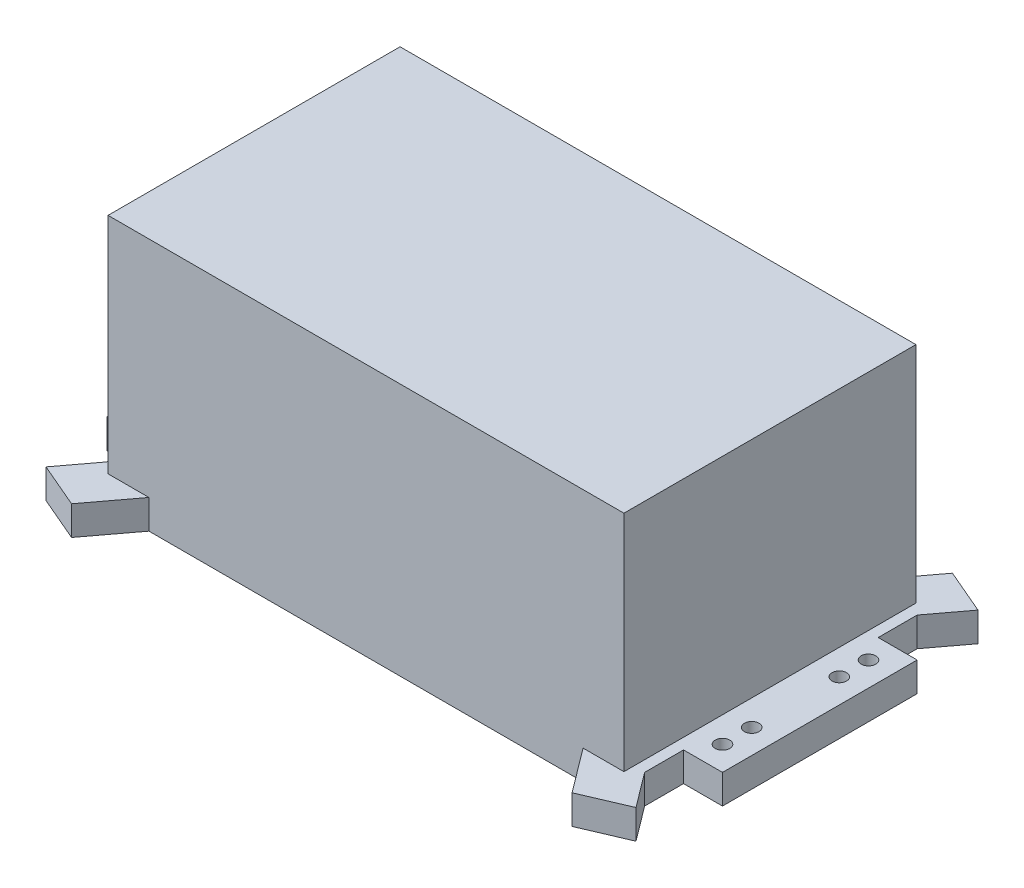
SolidWorks part; units mm, degrees
ref_plane "前视基准面" through (0, 0, 0) normal (0, 0, 1) x (1, 0, 0)
ref_plane "上视基准面" through (0, 0, 0) normal (0, 1, 0) x (1, 0, 0)
ref_plane "右视基准面" through (0, 0, 0) normal (1, 0, 0) x (0, 0, -1)
sketch "草图1" plane through (0, 0, 0) normal (0, 1, 0) x (1, 0, 0)
  line L0 (-65.7171, 0) -> (87.7991, 0) construction
  line L1 (44.6018, -30) -> (-44.6018, -30)
  line L3 (44.6018, 30) -> (-44.6018, 30)
  line L5 (53, -30) -> (-53, 30) construction
  line L6 (53, 30) -> (-53, -30) construction
  line L8 (63.25, -20) -> (63.25, 20)
  line L10 (-63.25, -20) -> (-63.25, 20)
  line L11 (63.25, 20) -> (55.25, 20)
  line L12 (55.25, 20) -> (55.25, 28)
  line L13 (55.25, 28) -> (60.6154, 35.1388)
  line L14 (60.6154, 35.1388) -> (51.4231, 39.0759)
  line L15 (51.4231, 39.0759) -> (44.6018, 30)
  line L16 (63.25, -20) -> (55.25, -20)
  line L17 (55.25, -20) -> (55.25, -28)
  line L18 (55.25, -28) -> (60.6154, -35.1388)
  line L19 (60.6154, -35.1388) -> (51.4231, -39.0759)
  line L20 (51.4231, -39.0759) -> (44.6018, -30)
  line L21 (0, -33.7082) -> (0, 42.5182) construction
  line L22 (-51.4231, -39.0759) -> (-44.6018, -30)
  line L23 (-60.6154, -35.1388) -> (-51.4231, -39.0759)
  line L24 (-55.25, -28) -> (-60.6154, -35.1388)
  line L25 (-55.25, -20) -> (-55.25, -28)
  line L26 (-63.25, -20) -> (-55.25, -20)
  line L27 (-63.25, 20) -> (-55.25, 20)
  line L28 (-55.25, 20) -> (-55.25, 28)
  line L29 (-55.25, 28) -> (-60.6154, 35.1388)
  line L30 (-51.4231, 39.0759) -> (-44.6018, 30)
  line L31 (-60.6154, 35.1388) -> (-51.4231, 39.0759)
  circle A0 centre (58.25, 15) radius 1.5
  circle A1 centre (-58.25, 15) radius 1.5
  circle A2 centre (58.25, 9) radius 1.5
  circle A3 centre (-58.25, 9) radius 1.5
  circle A4 centre (58.25, -9) radius 1.5
  circle A5 centre (58.25, -15) radius 1.5
  circle A6 centre (-58.25, -9) radius 1.5
  circle A7 centre (-58.25, -15) radius 1.5
  point P0 (0, 0)
  point P5 (0, 0)
  dimension "D5" = 3
  dimension "D6" = 3
  dimension "D7" = 3
  dimension "D8" = 3
  dimension "D1" = 60
  dimension "D2" = 106
  dimension "D3" = 40
  dimension "D4" = 126.5
  dimension "D9" = 8
  dimension "D10" = 8
  dimension "D11" = 10
extrude "凸台-拉伸1" add sketch "草图1" along normal blind 6
ref_plane "基准面1" through (0, 6, 0) normal (0, 1, 0) x (1, 0, 0)
sketch "草图2" plane through (0, 6, 0) normal (0, 1, 0) x (1, 0, 0)
  line L1 (53, -30) -> (-53, -30)
  line L2 (53, -30) -> (53, 30)
  line L3 (53, 30) -> (-53, 30)
  line L4 (-53, -30) -> (-53, 30)
  line L5 (53, -30) -> (-53, 30) construction
  line L6 (53, 30) -> (-53, -30) construction
  point P0 (0, 0)
  dimension "D1" = 60
  dimension "D2" = 106
extrude "凸台-拉伸2" add sketch "草图2" along normal blind 46
sketch "草图3" plane through (0, 0, -30) normal (0, 0, -1) x (-1, 0, 0)
  line L1 (-42.197, 39.6989) -> (-14.3671, 39.6989)
  line L2 (-42.197, 39.6989) -> (-42.197, 25.4323)
  line L3 (-42.197, 25.4323) -> (-14.3671, 25.4323)
  line L4 (-14.3671, 39.6989) -> (-14.3671, 25.4323)
  line L5 (-12.2572, 39.6989) -> (15.9746, 39.6989)
  line L6 (-12.2572, 39.6989) -> (-12.2572, 25.4323)
  line L7 (-12.2572, 25.4323) -> (15.9746, 25.4323)
  line L8 (15.9746, 39.6989) -> (15.9746, 25.4323)
  line L9 (-36.2693, 15.9882) -> (-30.3416, 15.9882)
  line L10 (-36.2693, 15.9882) -> (-36.2693, 12.9741)
  line L11 (-36.2693, 12.9741) -> (-30.3416, 12.9741)
  line L12 (-30.3416, 15.9882) -> (-30.3416, 12.9741)
  line L13 (-26.2224, 15.9882) -> (-19.491, 15.9882)
  line L14 (-26.2224, 15.9882) -> (-26.2224, 12.0699)
  line L15 (-26.2224, 12.0699) -> (-19.491, 12.0699)
  line L16 (-19.491, 15.9882) -> (-19.491, 12.0699)
  line L17 (-14.3671, 15.9882) -> (-7.6356, 15.9882)
  line L18 (-14.3671, 15.9882) -> (-14.3671, 12.0699)
  line L19 (-14.3671, 12.0699) -> (-7.6356, 12.0699)
  line L20 (-7.6356, 15.9882) -> (-7.6356, 12.0699)
  circle A0 centre (7.2338, 14.9835) radius 2.9136
  point P22 (-12.2572, 39.6989)
